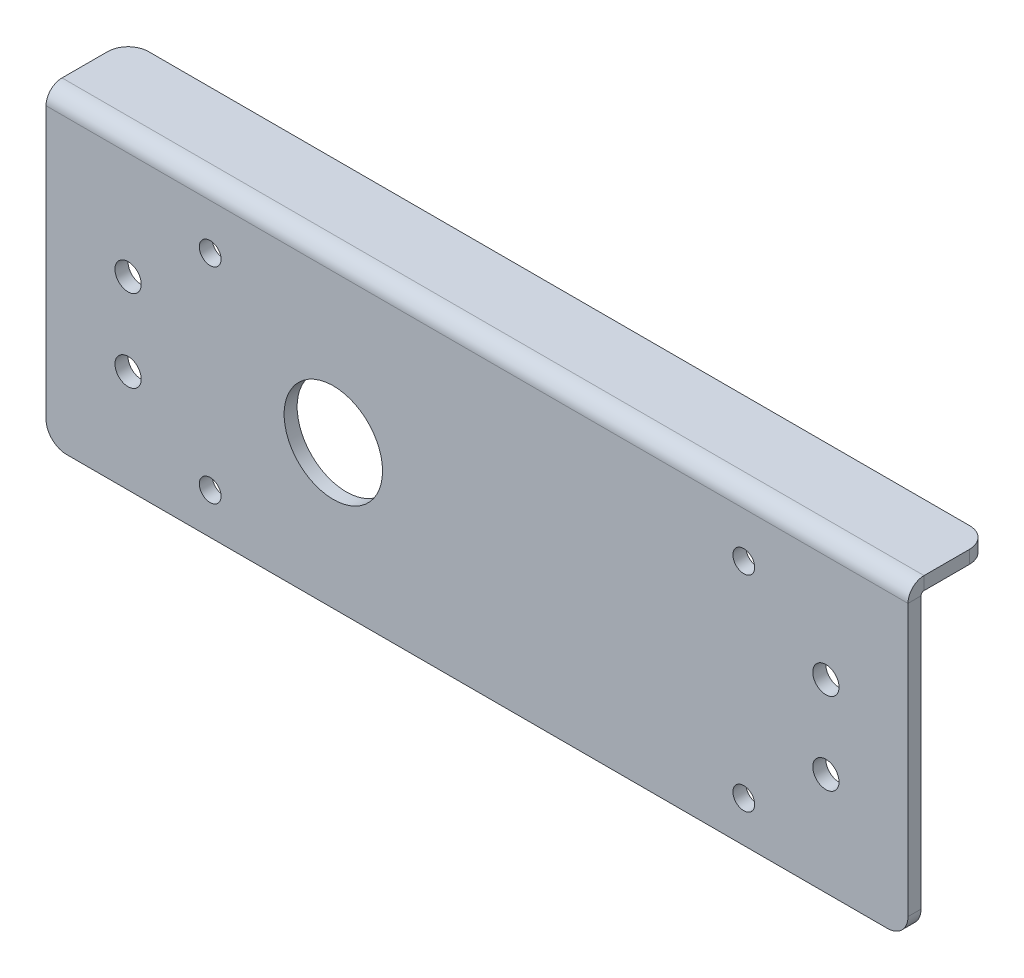
SolidWorks part; units mm, degrees
note: The reader was unsure of these and kept them because the rebuilt part matched: flange length of "Edge-Flange1".
material "5052-H32"
ref_plane "Front Plane" through (0, 0, 0) normal (0, 0, 1) x (1, 0, 0)
ref_plane "Top Plane" through (0, 0, 0) normal (0, 1, 0) x (1, 0, 0)
ref_plane "Right Plane" through (0, 0, 0) normal (1, 0, 0) x (0, 0, -1)
sketch "Sketch1" plane through (0, 0, 0) normal (0, 0, 1) x (1, 0, 0)
  line L0 (-30, 25) -> (100, 25) construction
  line L1 (-70, 40) -> (140, 40)
  line L2 (-70, 40) -> (-70, -35)
  line L3 (-70, -35) -> (140, -35)
  line L4 (140, 40) -> (140, -35)
  line L5 (-30, 25) -> (-30, -25) construction
  line L6 (35.3553, -35.3553) -> (0, 0) construction
  line L7 (-50, 10) -> (120, 10) construction
  line L8 (-50, 10) -> (-50, -10) construction
  line L9 (-50, -10) -> (120, -10) construction
  line L10 (120, 10) -> (120, -10) construction
  line L11 (0, 0) -> (50, 0) construction
  circle A0 centre (0, 0) radius 11.9875
  circle A1 centre (-30, 25) radius 2.5 construction
  circle A2 centre (100, 25) radius 2.5 construction
  circle A3 centre (-30, -25) radius 2.5 construction
  circle A4 centre (100, -25) radius 2.5 construction
  circle A5 centre (-50, 10) radius 3 construction
  circle A6 centre (-50, -10) radius 3 construction
  circle A7 centre (120, -10) radius 3 construction
  circle A8 centre (120, 10) radius 3 construction
  circle A9 centre (50, 0) radius 40 construction
  arc A10 (50, 0) -> (35.3553, -35.3553) centre (0, 0) cw construction
  circle A11 centre (35.3553, -35.3553) radius 40 construction
  point P20 (-50, 0)
  point P28 (-30, 0)
  point P32 (35, 40)
  point P34 (35, 10)
  dimension "D1" = 23.975
  dimension "D6" = 50
  dimension "D7" = 5
  dimension "D2" = 6
  dimension "D9" = 20
  dimension "D11" = 80
  dimension "D12" = 50
  dimension "D3" = 20
  dimension "D4" = 130
  dimension "D5" = 15
  dimension "D8" = 30
  dimension "D10" = 20
  dimension "D13" = 45
  dimension "D14" = 20
  dimension "D15" = 10
base flange "Base-Flange1" sketch "Sketch1" thickness 3.175 reverse thickness direction no parameters "D1"=0.7366
edge flange "Edge-Flange1" sketch "Sketch8" flange angle 90 flange length 20 flange position material inside bend radius 0.7366 thickness 3.175 relief rectangular parameters "D6"=10
sketch "Sketch8" plane through (0, 40, -3.175) normal (0, 1, 0) x (1, 0, 0)
  line L0 (140, 0) -> (-70, 0) construction
  line L1 (140, 0) -> (-70, 0)
  line L2 (-70, 0) -> (-70, 16.825)
  line L3 (-70, 16.825) -> (140, 16.825)
  line L4 (140, 16.825) -> (140, 0)
bend "EdgeBend1" bend radius 0.7366 bend angle 90 parameters "D5"=1
hole_wizard "M6 Clearance Hole2" positions "3DSketch1" profile "Sketch9" hole size "M6" standard "ANSI Metric" end condition up to next
sketch3d "3DSketch1"
  point P0 (-50, 10, 0)
  point P2 (-50, -10, 0)
  point P4 (120, -10, 0)
  point P6 (120, 10, 0)
  point P9 (120, 10, 0)
  point P11 (120, -10, 0)
  point P13 (-50, -10, 0)
  point P15 (-50, 10, 0)
sketch "Sketch9" plane through (-50, 10, 0) normal (1, 0, 0) x (0, -1, 0)
  line L0 (0, 0) -> (0, 3.175)
  line L1 (0, 3.175) -> (3.2, 3.175)
  line L2 (3.2, 3.175) -> (3.2, 0)
  line L5 (3.2, 0) -> (0, 0)
  line L11 (0, -6.35) -> (0, 107.95) construction
  dimension "Thru Hole Dia." = 6.4
  dimension "Thru Hole Depth" = 3.175
hole_wizard "M5 Clearance Hole1" positions "3DSketch2" profile "Sketch10" hole size "M5" standard "ANSI Metric" end condition up to next
sketch3d "3DSketch2"
  point P0 (-30, 25, 0)
  point P2 (-30, -25, 0)
  point P4 (100, -25, 0)
  point P6 (100, 25, 0)
  point P9 (100, 30, 0)
  point P11 (-30, 30, 0)
  point P13 (-30, -30, 0)
  point P15 (100, -30, 0)
sketch "Sketch10" plane through (-30, 25, 0) normal (1, 0, 0) x (0, -1, 0)
  line L0 (0, 0) -> (0, 3.175)
  line L1 (0, 3.175) -> (2.65, 3.175)
  line L2 (2.65, 3.175) -> (2.65, 0)
  line L5 (2.65, 0) -> (0, 0)
  line L11 (0, -6.35) -> (0, 107.95) construction
  dimension "Thru Hole Dia." = 5.3
  dimension "Thru Hole Depth" = 3.175
fillet "Fillet1" radius 5 4 edges at (140, 38.4125, -20) (-70, 38.4125, -20) (-70, -35, -1.5875) (140, -35, -1.5875)
sketch "Bend-Lines1" [suppressed] plane through (0, 0, 0) normal (0, 1, 0) x (1, 0, 0)
sketch "Bounding-Box1" [suppressed] plane through (0, 0, 0) normal (0, 1, 0) x (1, 0, 0)
sheet metal parameters "Sheet-Metal4" thickness 3.175 parameters "D1"=0.7366
flat pattern "Flat-Pattern4" [suppressed]
sketch "Bend-Lines2" plane through (0, 0, 0) normal (0, 1, 0) x (1, 0, 0)
sketch3d "Bounding-Box2" [suppressed]
  line L0 (70, -40, 0) -> (-140, -40, 0) construction
  line L1 (70, 40, 0) -> (-140, 40, 0) construction
  line L2 (70, -40, 0) -> (70, 40, 0) construction
  line L3 (-140, -40, 0) -> (-140, 40, 0) construction
sheet metal parameters "Sheet-Metal5" thickness 3.175 parameters "D1"=0.7366
flat pattern "Flat-Pattern4"
sketch "Bend-Lines2" plane through (0, 0, 0) normal (0, 0, 1) x (1, 0, 0)
  line L0 (140, 37.9137) -> (-70, 37.9137) construction
  line L1 (140, 37.9137) -> (-70, 37.9137) construction
sketch3d "Bounding-Box2" [suppressed]
  line L0 (-70, -40, 0) -> (140, -40, 0) construction
  line L1 (-70, 55.8275, 0) -> (140, 55.8275, 0) construction
  line L2 (-70, -40, 0) -> (-70, 55.8275, 0) construction
  line L3 (140, -40, 0) -> (140, 55.8275, 0) construction
bend of the flat pattern "Flatten-<EdgeBend1>1"
sheet metal parameters "Sheet-Metal6" thickness 3.175 parameters "D1"=0.7366
flat pattern "Flat-Pattern4"
sketch "Bend-Lines2" plane through (0, 0, 0) normal (0, 0, 1) x (1, 0, 0)
  line L0 (140, 37.9137) -> (-70, 37.9137) construction
  line L1 (140, 37.9137) -> (-70, 37.9137) construction
sketch3d "Bounding-Box2" [suppressed]
  line L0 (-70, -40, 0) -> (140, -40, 0) construction
  line L1 (-70, 55.8275, 0) -> (140, 55.8275, 0) construction
  line L2 (-70, -40, 0) -> (-70, 55.8275, 0) construction
  line L3 (140, -40, 0) -> (140, 55.8275, 0) construction
bend of the flat pattern "Flatten-<EdgeBend1>1"
sheet metal parameters "Sheet-Metal7" thickness 3.175 parameters "D1"=0.7366
flat pattern "Flat-Pattern4"
sketch "Bend-Lines2" plane through (0, 0, 0) normal (0, 0, 1) x (1, 0, 0)
  line L0 (140, 37.9137) -> (-70, 37.9137) construction
  line L1 (140, 37.9137) -> (-70, 37.9137) construction
sketch3d "Bounding-Box2" [suppressed]
  line L0 (-70, 55.8275, 0) -> (140, 55.8275, 0) construction
  line L1 (-70, -35, 0) -> (140, -35, 0) construction
  line L2 (-70, 55.8275, 0) -> (-70, -35, 0) construction
  line L3 (140, 55.8275, 0) -> (140, -35, 0) construction
bend of the flat pattern "Flatten-<EdgeBend1>1"
